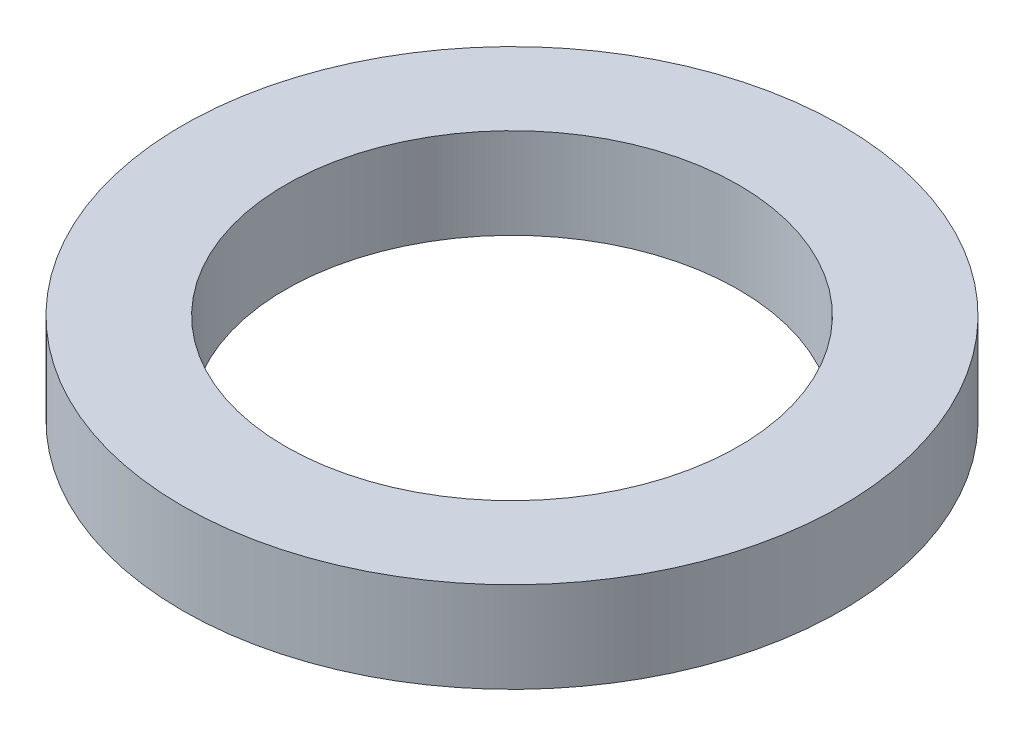
SolidWorks part; units mm, degrees
ref_plane "Front Plane" through (0, 0, 0) normal (0, 0, 1) x (1, 0, 0)
ref_plane "Top Plane" through (0, 0, 0) normal (0, 1, 0) x (1, 0, 0)
ref_plane "Right Plane" through (0, 0, 0) normal (1, 0, 0) x (0, 0, -1)
sketch "Sketch1" plane through (0, 0, 0) normal (0, 1, 0) x (1, 0, 0)
  circle A0 centre (0, 0) radius 40
  dimension "FLANGE_OD" = 80
extrude "Boss-Extrude1" add sketch "Sketch1" along normal blind 11
sketch "Sketch2" plane through (0, 0, 0) normal (0, 1, 0) x (1, 0, 0)
  circle A0 centre (0, 0) radius 27.5
  dimension "BORE_D" = 55
extrude "Cut-Extrude1" cut sketch "Sketch2" along normal through all
sketch "Sketch3" plane through (0, 11, 0) normal (0, 1, 0) x (1, 0, 0)
  circle A0 centre (0, 0) radius 18.2119 construction
  circle A1 centre (-18.2119, 0) radius 1.5032
  dimension "BOLT_D" = 3.0064
  dimension "BOLT_PCD" = 36.4238
extrude "Cut-Extrude2" cut sketch "Sketch3" against normal blind 10.6753 rebuild error yes
pattern_circular "CirPattern1" count 5 over 360 rebuild error yes
